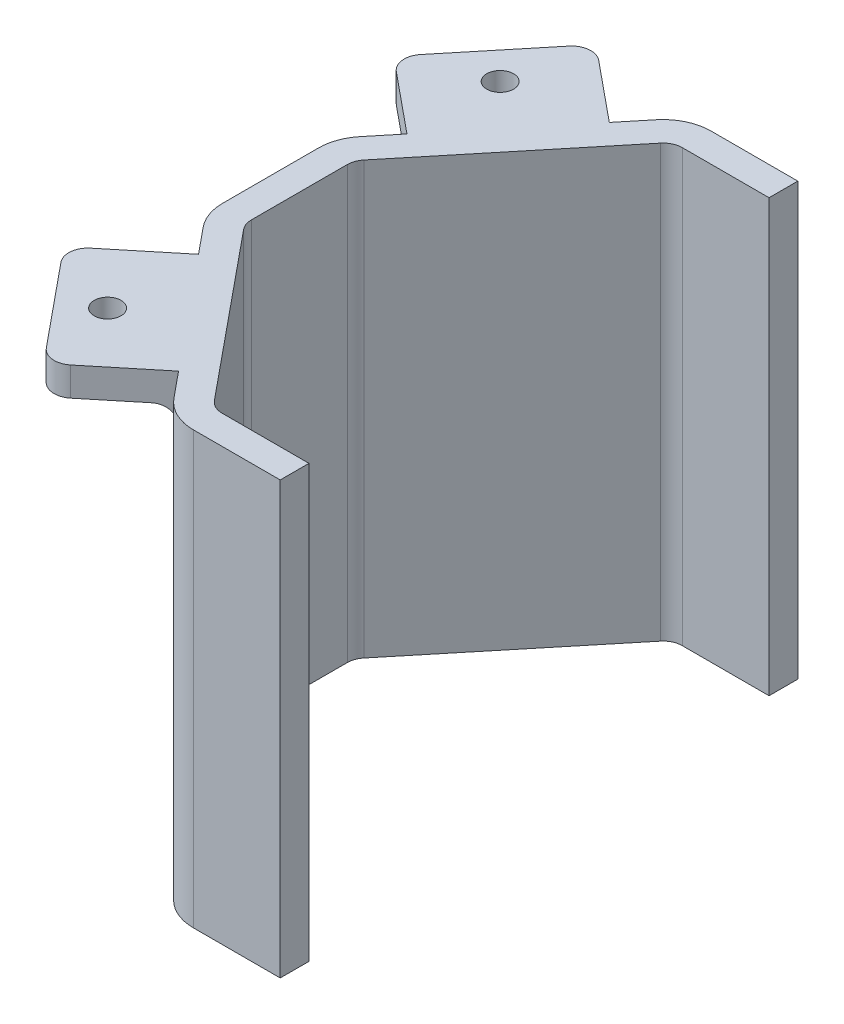
SolidWorks part; units mm, degrees
ref_plane "Front Plane" through (0, 0, 0) normal (0, 0, 1) x (1, 0, 0)
ref_plane "Top Plane" through (0, 0, 0) normal (0, 1, 0) x (1, 0, 0)
ref_plane "Right Plane" through (0, 0, 0) normal (1, 0, 0) x (0, 0, -1)
sketch "Sketch2" plane through (0, 0, 0) normal (0, 1, 0) x (1, 0, 0)
  line L0 (-6, 30) -> (6, 30)
  line L1 (6, 30) -> (6, 24)
  line L2 (6, 24) -> (2, 24)
  line L3 (2, 24) -> (2, -24)
  line L4 (2, -24) -> (6, -24)
  line L5 (6, -24) -> (6, -30)
  line L6 (6, -30) -> (-6, -30)
  line L7 (-6, -30) -> (-6, -24)
  line L8 (-6, -24) -> (-2, -24)
  line L9 (-2, -24) -> (-2, 24)
  line L10 (-2, 24) -> (-6, 24)
  line L11 (-6, 24) -> (-6, 30)
  point P12 (-2, 0)
  point P14 (0, 30)
  dimension "D2" = 60
  dimension "D3" = 6
  dimension "D4" = 4
sketch "Sketch3" plane through (0, 0, 0) normal (0, 1, 0) x (1, 0, 0)
  line L0 (-8, 24) -> (-17.0538, 24)
  line L1 (-18.6001, 23.2685) -> (-32.5463, 6.2685)
  line L2 (-33, 5) -> (-33, -5)
  line L3 (-32.5463, -6.2685) -> (-18.6001, -23.2685)
  line L4 (-17.0538, -24) -> (-8, -24)
  line L5 (-8, 24) -> (-8, -24) construction
  line L7 (-2, 24) -> (-6, 24) construction
  line L8 (-8, 24) -> (-18, 24) construction
  line L9 (-8, 27) -> (-17.0538, 27)
  line L10 (-20.9195, 25.1712) -> (-34.8657, 8.1712)
  line L11 (-36, 5) -> (-36, -5)
  line L12 (-34.8657, -8.1712) -> (-20.9195, -25.1712)
  line L13 (-17.0538, -27) -> (-8, -27)
  line L14 (-8, 27) -> (-8, 24)
  line L15 (-8, -27) -> (-8, -24)
  line L16 (-18, 24) -> (-33, 5.7154) construction
  line L17 (-18, -24) -> (-8, -24) construction
  line L18 (-33, -5.7154) -> (-18, -24) construction
  line L19 (-19.4192, -27) -> (-8, -27) construction
  line L20 (-36, -6.7885) -> (-19.4192, -27) construction
  line L21 (-8, 27) -> (-19.4192, 27) construction
  line L22 (-19.4192, 27) -> (-36, 6.7885) construction
  line L23 (-33, 5.7154) -> (-33, -5.7154) construction
  line L24 (-36, 6.7885) -> (-36, -6.7885) construction
  arc A0 (-17.0538, 24) -> (-18.6001, 23.2685) centre (-17.0538, 22) ccw
  arc A1 (-17.0538, -24) -> (-18.6001, -23.2685) centre (-17.0538, -22) cw
  arc A2 (-17.0538, -27) -> (-20.9195, -25.1712) centre (-17.0538, -22) cw
  arc A3 (-17.0538, 27) -> (-20.9195, 25.1712) centre (-17.0538, 22) ccw
  arc A4 (-32.5463, 6.2685) -> (-33, 5) centre (-31, 5) ccw
  arc A5 (-32.5463, -6.2685) -> (-33, -5) centre (-31, -5) cw
  arc A6 (-36, 5) -> (-34.8657, 8.1712) centre (-31, 5) cw
  arc A7 (-34.8657, -8.1712) -> (-36, -5) centre (-31, -5) cw
  point P2 (-8, 0)
  point P7 (-33, 0)
  point P21 (-18, 24)
  point P25 (-18, -24)
  point P38 (-46.9768, 7.7828)
  dimension "D6" = 2
  dimension "D7" = 2
  dimension "D8" = 5
  dimension "D9" = 5
  dimension "D10" = 2
  dimension "D4" = 2
  dimension "D12" = 5
  dimension "D13" = 5
  dimension "D1" = 2
  dimension "D2" = 10
  dimension "D3" = 25
  dimension "D11" = 10
  dimension "D5" = 3
extrude "Boss-Extrude1" add sketch "Sketch3" along normal blind 45
sketch "Sketch4" plane through (0, 45, 0) normal (0, -1, 0) x (1, 0, 0)
  line L0 (-23.1357, 22.4697) -> (-30.867, 28.8122)
  line L1 (-34.8657, 8.1712) -> (-20.9195, 25.1712) construction
  line L2 (-30.867, 28.8122) -> (-40.3807, 17.2152)
  line L3 (-40.3807, 17.2152) -> (-32.6494, 10.8728)
  line L4 (-23.1357, 22.4697) -> (-32.6494, 10.8728)
  line L5 (-32.6494, -10.8728) -> (-40.3807, -17.2152)
  line L6 (-20.9195, -25.1712) -> (-34.8657, -8.1712) construction
  line L7 (-40.3807, -17.2152) -> (-30.867, -28.8122)
  line L8 (-30.867, -28.8122) -> (-23.1357, -22.4697)
  line L9 (-23.1357, -22.4697) -> (-32.6494, -10.8728)
  point P7 (-27.8926, -16.6712)
  point P8 (-27.8926, -16.6712)
  point P21 (-27.8926, 16.6712)
  point P22 (-27.8926, 16.6712)
  dimension "D1" = 10
  dimension "D2" = 10
  dimension "D3" = 15
  dimension "D4" = 15
extrude "Boss-Extrude2" add sketch "Sketch4" along normal blind 3
fillet "Fillet1" radius 2 6 edges at (-27.8926, 42, -16.6712) (-30.867, 43.5, -28.8122) (-40.3807, 43.5, -17.2152) (-27.8926, 42, 16.6712) (-30.867, 43.5, 28.8122) (-40.3807, 43.5, 17.2152)
sketch "Sketch5" plane through (0, 42, 0) normal (0, -1, 0) x (1, 0, 0)
  line L0 (-38.8345, 15.9467) -> (-34.1957, 12.1413) construction
  line L1 (-32.1355, 27.2659) -> (-39.1122, 18.7615) construction
  circle A0 centre (-32.5314, 20.4767) radius 1.4
  point P2 (0, 0)
  dimension "D3" = 2.8
  dimension "D1" = 4
  dimension "D2" = 7.5
extrude "Cut-Extrude1" cut sketch "Sketch5" against normal through all
mirror "Mirror1" about plane through (0, 0, 0) normal (0, 0, 1) of "Cut-Extrude1"
